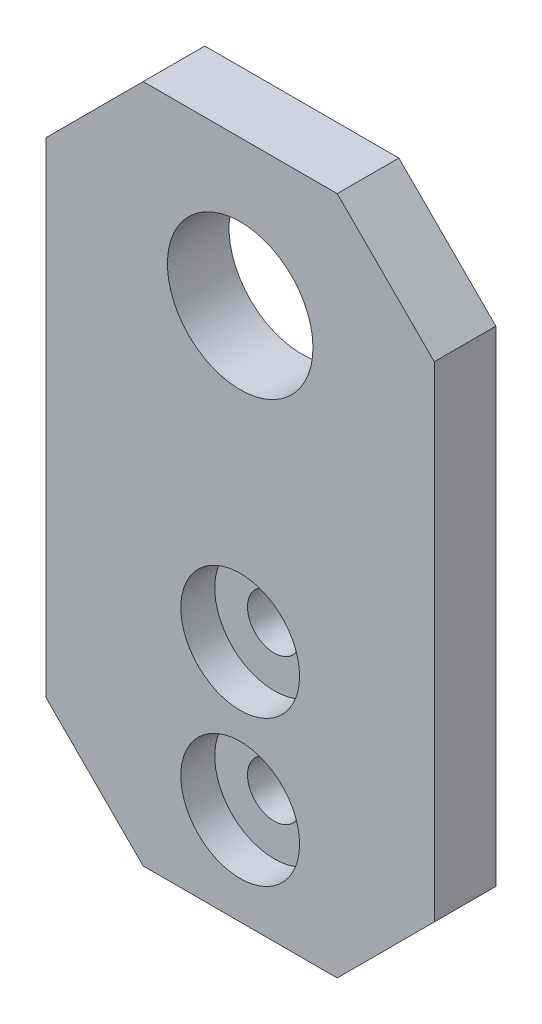
SolidWorks part; units mm, degrees
material "6061 Alloy"
ref_plane "Front Plane" through (0, 0, 0) normal (0, 0, 1) x (1, 0, 0)
ref_plane "Top Plane" through (0, 0, 0) normal (0, 1, 0) x (1, 0, 0)
ref_plane "Right Plane" through (0, 0, 0) normal (1, 0, 0) x (0, 0, -1)
sketch "Sketch1" plane through (0, 0, 0) normal (0, 0, 1) x (1, 0, 0)
  line L0 (0, 35) -> (0, -35) construction
  line L1 (-20, -35) -> (20, -35)
  line L2 (-20, -35) -> (-20, 35)
  line L3 (-20, 35) -> (20, 35)
  line L4 (20, -35) -> (20, 35)
  line L5 (-20, -35) -> (20, 35) construction
  line L6 (-20, 35) -> (20, -35) construction
  circle A0 centre (0, 20) radius 7.5
  circle A1 centre (0, -10) radius 2.5 construction
  circle A2 centre (0, -25) radius 2.5 construction
  point P4 (0, 0)
  dimension "D3" = 15
  dimension "D4" = 5
  dimension "D5" = 5
  dimension "D1" = 40
  dimension "D2" = 70
  dimension "D6" = 10
  dimension "D7" = 15
  dimension "D8" = 55
extrude "Boss-Extrude1" add sketch "Sketch1" along normal blind 6.35
hole_wizard "CBORE for M5 Hex Head Bolt1" positions "Sketch4" profile "Sketch5" counterbore size "M5" standard "ISO" end condition through all
sketch "Sketch4" plane through (0, 0, 6.35) normal (0, 0, 1) x (1, 0, 0)
  point P0 (0, -10)
  point P3 (0, -25)
sketch "Sketch5" plane through (0, -10, 6.35) normal (1, 0, 0) x (0, -1, 0)
  line L0 (0, 0) -> (0, 6.35)
  line L1 (0, 6.35) -> (2.75, 6.35)
  line L3 (2.75, 6.35) -> (2.75, 3.5)
  line L4 (2.75, 3.5) -> (6.119, 3.5)
  line L5 (6.119, 3.5) -> (6.119, 0)
  line L7 (6.119, 0) -> (0, 0)
  line L11 (0, -6.35) -> (0, 107.95) construction
  dimension "Thru Hole Dia." = 5.5
  dimension "Thru Hole Depth" = 6.35
  dimension "C'Bore Dia." = 12.238
  dimension "C'Bore Depth" = 3.5
chamfer "Chamfer1" distance 10 angle 45 4 edges at (20, -35, 3.175) (-20, -35, 3.175) (20, 35, 3.175) (-20, 35, 3.175)
